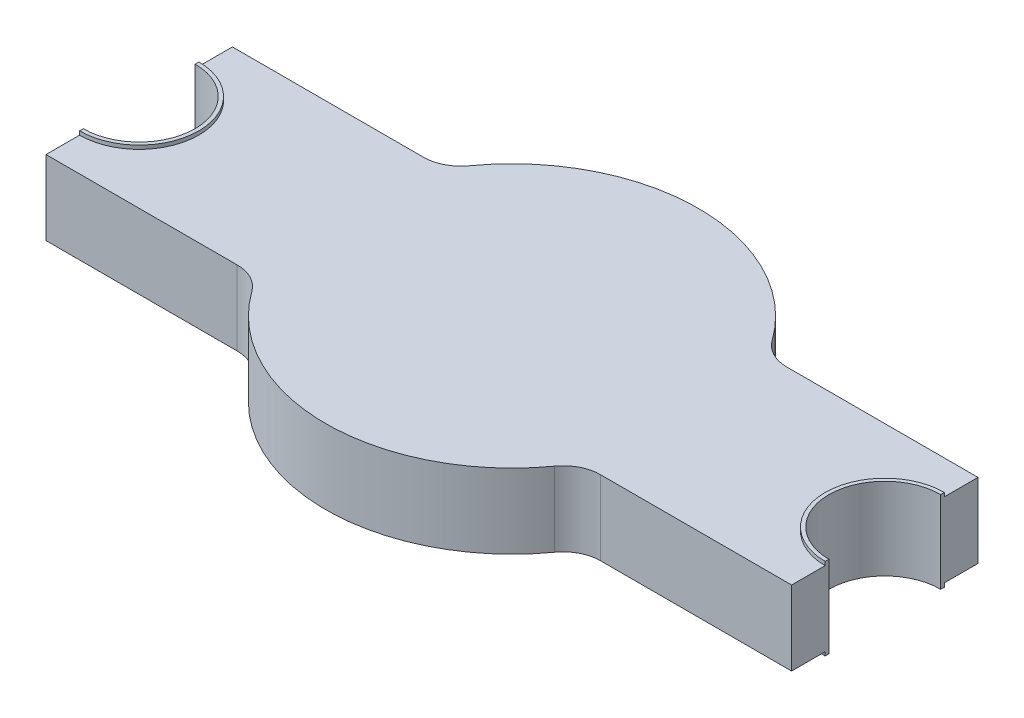
SolidWorks part; units mm, degrees
material "201 退火不锈钢 (SS)"
ref_plane "前视基准面" through (0, 0, 0) normal (0, 0, 1) x (1, 0, 0)
ref_plane "上视基准面" through (0, 0, 0) normal (0, 1, 0) x (1, 0, 0)
ref_plane "右视基准面" through (0, 0, 0) normal (1, 0, 0) x (0, 0, -1)
sketch "草图1" plane through (0, 0, 0) normal (0, 1, 0) x (1, 0, 0)
  line L1 (-100, -25) -> (100, -25)
  line L2 (-100, -25) -> (-100, 25)
  line L3 (-100, 25) -> (100, 25)
  line L4 (100, -25) -> (100, 25)
  line L5 (-100, -25) -> (100, 25) construction
  line L6 (-100, 25) -> (100, -25) construction
  circle A0 centre (0, 0) radius 50
  point P0 (0, 0)
  dimension "D1" = 200
  dimension "D2" = 50
extrude "凸台-拉伸1" add sketch "草图1" along normal blind 20 contours L3 A0 | L1 A0 L3 | L1 A0 | A0 L1 L4 L3 | A0 L3 L2 L1 region at (-73.8779, 0, 0) region at (0, 0, 0) region at (0, 0, 35.251) region at (73.8779, 0, 0) region at (0, 0, -35.251)
sketch "草图2" plane through (0, 0, 0) normal (0, 1, 0) x (1, 0, 0)
  circle A0 centre (0, 0) radius 40
fillet "圆角1" radius 10 1 edges at (-43.3013, 10, 25)
fillet "圆角2" radius 10 3 edges at (43.3013, 10, 25) (43.3013, 10, -25) (-43.3013, 10, -25)
sketch "草图3" plane through (0, 0, 0) normal (0, 1, 0) x (1, 0, 0)
  line L0 (-100, -25) -> (-100, 25) construction
  line L1 (0, 0) -> (0, 40)
  circle A0 centre (-100, 0) radius 15
  circle A2 centre (0, 0) radius 40 construction
  circle A3 centre (100, 0) radius 15
extrude "切除-拉伸1" cut sketch "草图3" along normal blind 20 contours A0 | A3 region at (-100, 0, 0) region at (100, 0, 0)
sketch "草图4" plane through (0, 0, 0) normal (0, 1, 0) x (1, 0, 0)
  line L0 (-100, 16) -> (-100, 15)
  line L1 (-100, -15) -> (-100, -16)
  line L2 (0, 0) -> (0, 50)
  line L3 (100, -15) -> (100, -16)
  line L4 (100, 16) -> (100, 15)
  circle A0 centre (-100, 0) radius 16
  circle A1 centre (-100, 0) radius 15
  arc A2 (40.6116, 29.1667) -> (-40.6116, 29.1667) centre (0, 0) ccw construction
  circle A3 centre (100, 0) radius 15
  circle A4 centre (100, 0) radius 16
extrude "凸台-拉伸2" add sketch "草图4" along normal blind 21 and the other way blind 1 contours A1 L1 A0 L0 | A4 L3 A3 L4 region at (-88.9393, 0, -11.0607) region at (99.6422, 0, 15.5)
extrude "切除-拉伸2" cut sketch "草图2" along normal blind 15
sketch "草图5" plane through (0, 0, 0) normal (0, 1, 0) x (1, 0, 0)
  circle A0 centre (0, 0) radius 30
  circle A1 centre (0, 0) radius 15
  circle A2 centre (0, 0) radius 10
extrude "凸台-拉伸3" add sketch "草图5" along normal blind 15 contours A0
extrude "凸台-拉伸4" add sketch "草图5<3>" against normal blind 10 contours A1 A2 region at (-14.5757, 0, 0)
sketch "草图5<3>" plane through (0, 0, 0) normal (0, 1, 0) x (1, 0, 0) same geometry as "草图5"
